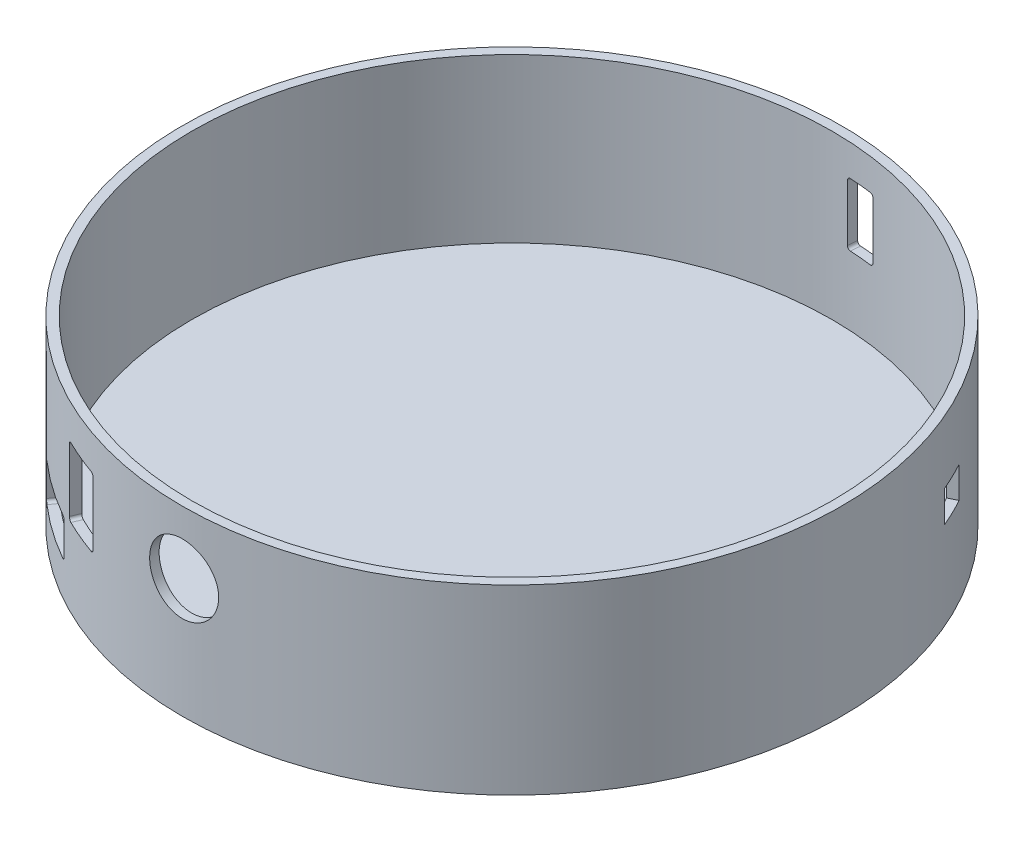
SolidWorks part; units mm, degrees
ref_plane "Přední rovina" through (0, 0, 0) normal (0, 0, 1) x (1, 0, 0)
ref_plane "Horní rovina" through (0, 0, 0) normal (0, 1, 0) x (1, 0, 0)
ref_plane "Pravá rovina" through (0, 0, 0) normal (1, 0, 0) x (0, 0, -1)
sketch "Skica1" plane through (0, 0, 0) normal (0, 1, 0) x (1, 0, 0)
  circle A0 centre (0, 0) radius 51
  circle A1 centre (0, 0) radius 52.5
  dimension "D1" = 102
  dimension "D2" = 105
extrude "Přidat vysunutím1" add sketch "Skica1" along normal blind 26 and the other way blind 3
extrude "Přidat vysunutím3" add sketch "Skica1<3>" against normal blind 3 contours A0 region at (0, 0, 0)
sketch "Skica1<3>" plane through (0, 0, 0) normal (0, 1, 0) x (1, 0, 0) same geometry as "Skica1"
sketch "Skica3" plane through (0, 0, 0) normal (0, 1, 0) x (1, 0, 0)
  line L0 (0, 55.3797) -> (0, -57.4308) construction
  line L1 (-58.5931, 0) -> (71.4466, 0) construction
  line L2 (-24.5, -44.7297) -> (-25.9432, -46.7711)
  line L3 (-24.5, -44.7297) -> (-34, -38.0132)
  line L4 (-25.9432, -46.7711) -> (-35.4432, -40.0545)
  line L5 (-34, -38.0132) -> (-35.4432, -40.0545)
  circle A0 centre (0, 0) radius 51 construction
  dimension "D3" = 2.5
  dimension "D1" = 24.5
  dimension "D2" = 34
extrude "Odebrat vysunutím1" cut sketch "Skica3" along normal blind 6 from offset 2.5 contours L4 L5 L3 L2
sketch "Skica4" plane through (0, 0, 0) normal (0, 1, 0) x (1, 0, 0)
  line L0 (0, 56.2672) -> (0, -68.9333) construction
  line L1 (-71.9325, 0) -> (69.8435, 0) construction
  line L2 (-16.5, -48.2571) -> (-17.4705, -50.5611)
  line L3 (-16.5, -48.2571) -> (-23, -45.5192)
  line L4 (-17.4705, -50.5611) -> (-23.9705, -47.8232)
  line L5 (-23, -45.5192) -> (-23.9705, -47.8232)
  circle A0 centre (0, 0) radius 51 construction
  dimension "D1" = 16.5
  dimension "D2" = 23
  dimension "D3" = 2.5
extrude "Odebrat vysunutím2" cut sketch "Skica4" along normal blind 11 from offset 9.5
fillet "Zaoblit1" radius 0.5 4 edges at (-34.4357, 8.5, 38.6295) (-24.9357, 8.5, 45.3461) (-24.9357, 2.5, 45.3461) (-34.4357, 2.5, 38.6295)
fillet "Zaoblit2" radius 0.5 4 edges at (-16.7918, 9.5, 48.9499) (-16.7918, 20.5, 48.9499) (-23.2918, 20.5, 46.212) (-23.2918, 9.5, 46.212)
sketch "Skica5" plane through (0, 0, 0) normal (0, 1, 0) x (1, 0, 0)
  line L0 (0, 58.7255) -> (0, -61.7236) construction
  line L1 (-65.0517, 0) -> (72.3942, 0) construction
  line L2 (2.5, 50.9387) -> (2.7341, 53.4387)
  line L3 (2.5, 50.9387) -> (7, 50.5173)
  line L4 (2.7341, 53.4387) -> (7.2341, 53.0173)
  line L5 (7, 50.5173) -> (7.2341, 53.0173)
  circle A0 centre (0, 0) radius 51 construction
  circle A1 centre (0, 0) radius 51 construction
  dimension "D1" = 2.5
  dimension "D2" = 7
  dimension "D3" = 2.5
extrude "Odebrat vysunutím3" cut sketch "Skica5" along normal blind 10 from offset 11
ref_plane "Rovina1" through (0, 16, 0) normal (0, 1, 0) x (1, 0, 0)
fillet "Zaoblit3" radius 0.5 4 edges at (7.07, 21, -51.2648) (2.57, 21, -51.6861) (2.57, 11, -51.6861) (7.07, 11, -51.2648)
sketch "Skica6" plane through (0, 16, 0) normal (0, 1, 0) x (1, 0, 0)
  line L0 (0, 58.2114) -> (0, -67.2442) construction
  line L1 (-10, 60.2187) -> (-10, -64.7351) construction
  line L2 (8.5, 58.2114) -> (8.5, -67.2442) construction
  line L3 (-5.5, -50) -> (0, -50)
  line L4 (-5.5, -52.5) -> (0, -52.5)
  line L5 (-5.5, -50) -> (-5.5, -52.5)
  line L6 (0, -50) -> (0, -52.5)
  circle A2 centre (0, 0) radius 52.5 construction
  dimension "D1" = 10
  dimension "D2" = 8.5
  dimension "D3" = 2.5
  dimension "D5" = 5.5
revolve "Odebrat rotací1" cut sketch "Skica6" angle 360 about L0
sketch "Skica7" plane through (0, 16, 0) normal (0, 1, 0) x (1, 0, 0)
  line L0 (-67.9973, 0) -> (85.127, 0) construction
  line L1 (46.9148, 20) -> (44.7309, 24.4978)
  line L2 (46.9148, 20) -> (49.1637, 21.0919)
  line L3 (44.7309, 24.4978) -> (46.9798, 25.5898)
  line L4 (49.1637, 21.0919) -> (46.9798, 25.5898)
  circle A0 centre (0, 0) radius 51 construction
  dimension "D1" = 20
  dimension "D2" = 2.5
  dimension "D3" = 5
extrude "Odebrat vysunutím4" cut sketch "Skica7" against normal blind 5
equation "\"ĚŠ\"=24.1145"
